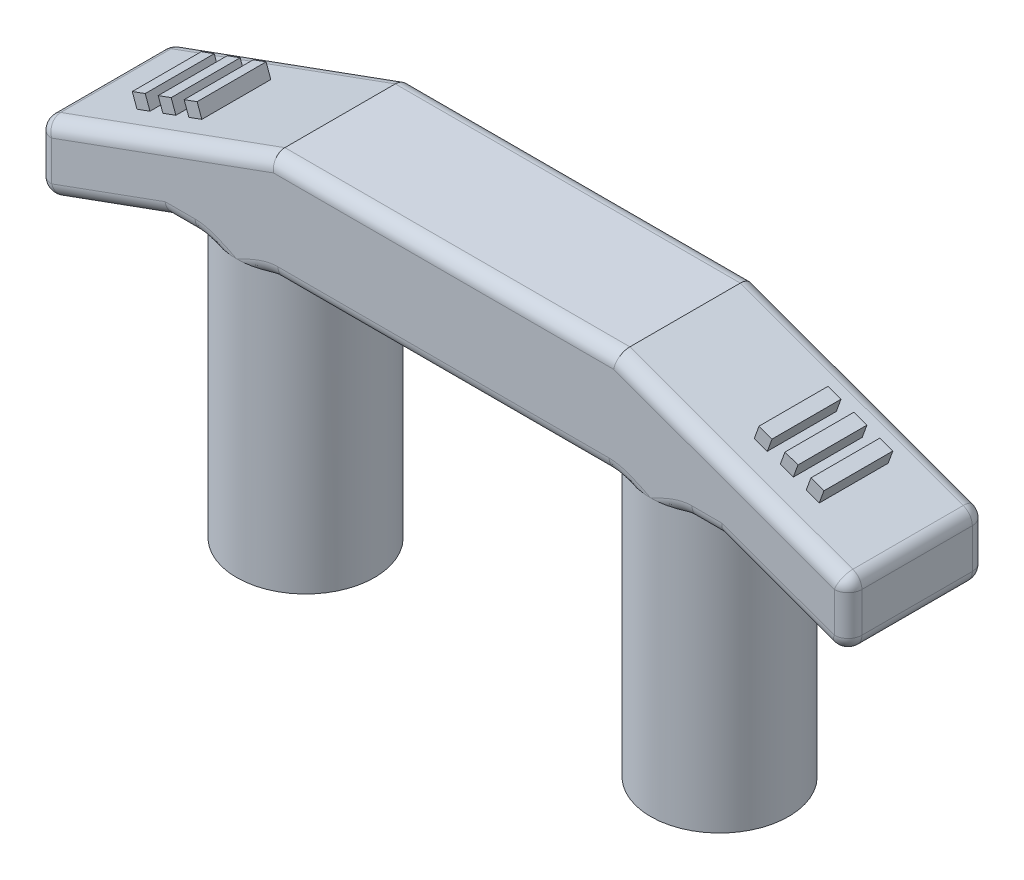
SolidWorks part; units mm, degrees
material "Polyetheretherketone (PEEK)"
ref_plane "Front Plane" through (0, 0, 0) normal (0, 0, 1) x (1, 0, 0)
ref_plane "Top Plane" through (0, 0, 0) normal (0, 1, 0) x (1, 0, 0)
ref_plane "Right Plane" through (0, 0, 0) normal (1, 0, 0) x (0, 0, -1)
sketch "Sketch1" plane through (0, 0, 0) normal (0, 1, 0) x (1, 0, 0)
  circle A0 centre (-38.1, 0) radius 12.7
  circle A1 centre (38.1, 0) radius 12.7
  dimension "D1" = 25.4
  dimension "D2" = 25.4
  dimension "D3" = 38.1
  dimension "D4" = 38.1
extrude "Boss-Extrude1" add sketch "Sketch1" along normal blind 50.8
sketch "Sketch3" plane through (0, 0, 0) normal (0, 0, 1) x (1, 0, 0)
  line L0 (-50.8, 50.8) -> (-74.6682, 42.1127)
  line L1 (-74.6682, 42.1127) -> (-74.6682, 54.8127)
  line L2 (-74.6682, 54.8127) -> (-31.75, 70.4336)
  line L3 (-31.75, 70.4336) -> (31.75, 70.4336)
  line L4 (31.75, 70.4336) -> (74.4553, 54.8902)
  line L5 (74.4553, 54.8902) -> (74.4553, 42.1902)
  line L9 (-50.8, 50.8) -> (-50.8, 0) construction
  line L11 (-50.8, 50.8) -> (50.8, 50.8)
  line L12 (50.8, 50.8) -> (74.4553, 42.1902)
  line L13 (50.8, 0) -> (50.8, 50.8) construction
  dimension "D1" = 70
  dimension "D2" = 70
  dimension "D3" = 25.4
  dimension "D4" = 12.7
  dimension "D5" = 12.7
  dimension "D6" = 63.5
extrude "Boss-Extrude2" add sketch "Sketch3" along normal mid plane 25.4
fillet "Fillet2" radius 2.54 24 edges at (0, 50.8, -12.7) (44.45, 50.8, -12.7) (62.6276, 46.4951, -12.7) (74.4553, 48.5402, -12.7) (53.1026, 62.6619, -12.7) (0, 70.4336, -12.7) (-53.2091, 62.6232, -12.7) (-74.6682, 48.4627, -12.7) (-62.7341, 46.4563, -12.7) (-44.45, 50.8, -12.7) (-62.7341, 46.4563, 12.7) (-74.6682, 48.4627, 12.7) (-53.2091, 62.6232, 12.7) (0, 70.4336, 12.7) (53.1026, 62.6619, 12.7) (74.4553, 48.5402, 12.7) (62.6276, 46.4951, 12.7) (44.45, 50.8, 12.7) (-44.45, 50.8, 12.7) (0, 50.8, 12.7) (74.4553, 42.1902, 0) (74.4553, 54.8902, 0) (-74.6682, 54.8127, 0) (-74.6682, 42.1127, 0)
sketch "Sketch4" plane through (-26.351, 72.3987, 0) normal (-0.342, 0.9397, 0) x (0.9397, 0.342, 0)
  line L0 (-33.6855, 6.35) -> (-31.1455, 6.35)
  line L1 (-38.7655, 6.35) -> (-36.2255, 6.35)
  line L2 (-38.7655, 6.35) -> (-38.7655, -6.35)
  line L3 (-38.7655, -6.35) -> (-36.2255, -6.35)
  line L4 (-36.2255, 6.35) -> (-36.2255, -6.35)
  line L5 (-33.6855, 6.35) -> (-33.6855, -6.35)
  line L6 (-33.6855, -6.35) -> (-31.1455, -6.35)
  line L7 (-31.1455, 6.35) -> (-31.1455, -6.35)
  line L8 (-28.6055, 6.35) -> (-26.0655, 6.35)
  line L9 (-28.6055, 6.35) -> (-28.6055, -6.35)
  line L10 (-28.6055, -6.35) -> (-26.0655, -6.35)
  line L11 (-26.0655, 6.35) -> (-26.0655, -6.35)
  line L12 (-5.7455, -10.16) -> (-5.7455, 10.16) construction
  line L13 (-5.7455, 10.16) -> (-49.6396, 10.16) construction
  dimension "D1" = 2.54
  dimension "D2" = 12.7
  dimension "D3" = 2.54
  dimension "D4" = 12.7
  dimension "D5" = 2.54
  dimension "D6" = 12.7
  dimension "D7" = 25.4
  dimension "D8" = 3.81
  dimension "D9" = 7.62
  dimension "D10" = 2.54
extrude "Boss-Extrude3" add sketch "Sketch4" along normal blind 2.54
mirror "Mirror1" about plane through (0, 0, 0) normal (1, 0, 0) of "Boss-Extrude3"
sketch "Sketch5" plane through (0, 50.8, 0) normal (0, -1, 0) x (1, 0, 0)
  line L0 (-19.05, 9.525) -> (-19.05, -9.525)
  arc A1 (-19.05, 9.525) -> (-19.05, -9.525) centre (-28.575, 0) cw
  dimension "D3" = 19.05
  dimension "D1" = 13.4704
  dimension "D2" = 19.05
  dimension "D4" = 28.575
revolve "Revolve1" add sketch "Sketch5" angle 360 about L0
pattern_linear "LPattern1" count 5 spacing 8.89 along (1, 0, 0) of "Revolve1"
